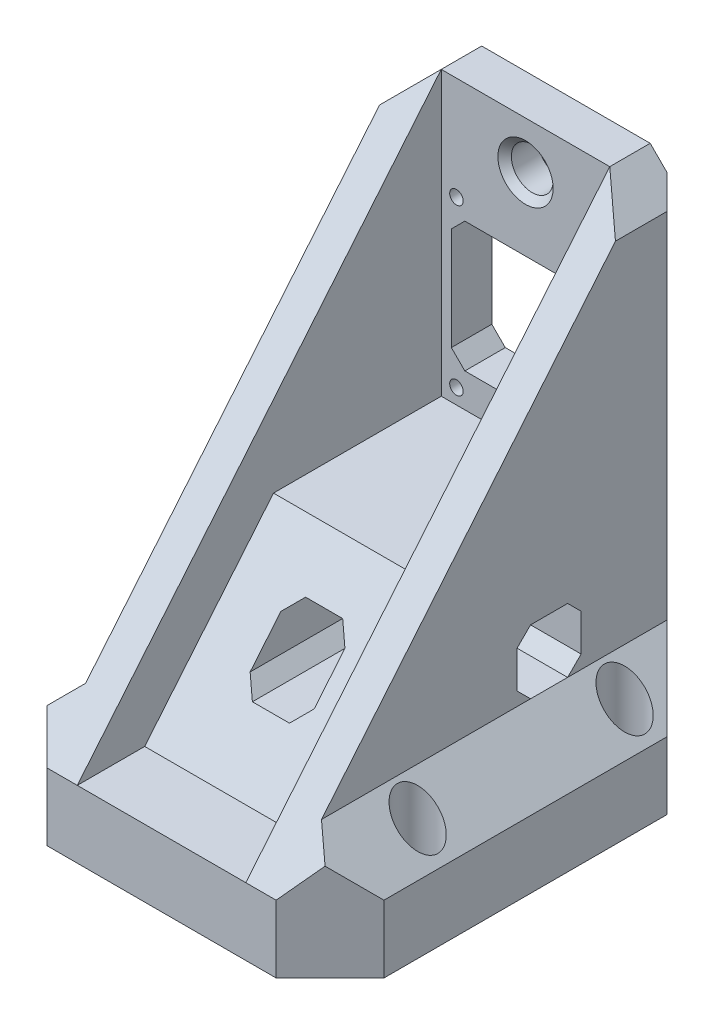
SolidWorks part; units mm, degrees
ref_plane "Front Plane" through (0, 0, 0) normal (0, 0, 1) x (1, 0, 0)
ref_plane "Top Plane" through (0, 0, 0) normal (0, 1, 0) x (1, 0, 0)
ref_plane "Right Plane" through (0, 0, 0) normal (1, 0, 0) x (0, 0, -1)
sketch "Sketch1" plane through (0, 0, 0) normal (0, 1, 0) x (1, 0, 0)
  line L1 (-25, 30) -> (25, 30)
  line L2 (-25, 30) -> (-25, -30)
  line L3 (-25, -30) -> (25, -30)
  line L4 (25, 30) -> (25, -30)
  line L5 (-25, 30) -> (25, -30) construction
  line L6 (-25, -30) -> (25, 30) construction
  point P0 (0, 0)
  dimension "D1" = 50
  dimension "D2" = 60
extrude "Boss-Extrude1" add sketch "Sketch1" along normal blind 10
sketch "Sketch2" plane through (0, 0, 0) normal (0, 1, 0) x (1, 0, 0)
  line L0 (-25, -30) -> (25, -30) construction
  line L1 (-21, -13) -> (21, -13) construction
  line L2 (-21, -13) -> (-21, 17.7) construction
  line L3 (-21, 17.7) -> (21, 17.7) construction
  line L4 (21, -13) -> (21, 17.7) construction
  line L5 (-21, -13) -> (21, 17.7) construction
  line L6 (-21, 17.7) -> (21, -13) construction
  circle A0 centre (-21, 17.7) radius 1.5
  circle A1 centre (-21, -13) radius 1.5
  circle A2 centre (21, 17.7) radius 1.5
  circle A3 centre (21, -13) radius 1.5
  point P0 (0, 2.35)
  dimension "D4" = 3
  dimension "D1" = 42
  dimension "D2" = 30.7
  dimension "D3" = 17
extrude "Cut-Extrude1" cut sketch "Sketch2" along normal blind 6
sketch "Sketch3" plane through (0, 6, 0) normal (0, -1, 0) x (1, 0, 0)
  circle A0 centre (-21, 13) radius 3
  circle A1 centre (21, 13) radius 3
  circle A2 centre (21, -17.7) radius 3
  circle A3 centre (-21, -17.7) radius 3
  dimension "D1" = 6
extrude "Cut-Extrude2" cut sketch "Sketch3" against normal up to next
sketch "Sketch5" plane through (0, 10, 0) normal (0, 1, 0) x (1, 0, 0)
  line L0 (25, 30) -> (-25, 30) construction
  line L1 (-12.5, 24) -> (12.5, 24)
  line L2 (-12.5, 24) -> (-12.5, 30)
  line L3 (-12.5, 30) -> (12.5, 30)
  line L4 (12.5, 24) -> (12.5, 30)
  line L5 (-12.5, 24) -> (12.5, 30) construction
  line L6 (-12.5, 30) -> (12.5, 24) construction
  point P0 (0, 27)
  dimension "D1" = 6
  dimension "D2" = 25
extrude "Boss-Extrude3" add sketch "Sketch5" along normal blind 65
sketch "Sketch6" plane through (0, 0, -30) normal (0, 0, -1) x (-1, 0, 0)
  line L1 (-11, 38) -> (11, 38)
  line L2 (-11, 38) -> (-11, 57.25)
  line L3 (-11, 57.25) -> (11, 57.25)
  line L4 (11, 38) -> (11, 57.25)
  line L5 (-11, 38) -> (11, 57.25) construction
  line L6 (-11, 57.25) -> (11, 38) construction
  line L7 (-12.5, 75) -> (12.5, 75) construction
  point P0 (0, 47.625)
  dimension "D1" = 22
  dimension "D2" = 19.25
  dimension "D3" = 17.75
extrude "Cut-Extrude3" cut sketch "Sketch6" against normal up to next
sketch "Sketch7" plane through (0, 0, -24) normal (0, 0, 1) x (1, 0, 0)
  line L1 (-10.25, 35.25) -> (10.25, 35.25) construction
  line L2 (-10.25, 35.25) -> (-10.25, 59.7) construction
  line L3 (-10.25, 59.7) -> (10.25, 59.7) construction
  line L4 (10.25, 35.25) -> (10.25, 59.7) construction
  line L5 (-10.25, 35.25) -> (10.25, 59.7) construction
  line L6 (-10.25, 59.7) -> (10.25, 35.25) construction
  line L7 (-12.5, 75) -> (12.5, 75) construction
  circle A0 centre (10.25, 35.25) radius 1
  circle A1 centre (-10.25, 35.25) radius 1
  circle A2 centre (-10.25, 59.7) radius 1
  circle A3 centre (10.25, 59.7) radius 1
  point P0 (0, 47.475)
  dimension "D4" = 2
  dimension "D1" = 20.5
  dimension "D2" = 24.45
  dimension "D3" = 15.3
extrude "Cut-Extrude4" cut sketch "Sketch7" against normal blind 2.5
sketch "Sketch8" plane through (0, 0, -26.5) normal (0, 0, 1) x (1, 0, 0)
  circle A0 centre (-10.25, 59.7) radius 2
  circle A1 centre (10.25, 59.7) radius 2
  circle A2 centre (10.25, 35.25) radius 2
  circle A3 centre (-10.25, 35.25) radius 2
  dimension "D1" = 4
extrude "Cut-Extrude5" cut sketch "Sketch8" against normal up to next
sketch "Sketch9" plane through (12.5, 0, 0) normal (1, 0, 0) x (0, 0, -1)
  line L0 (30, 75) -> (24, 75)
  line L4 (-30, 10) -> (30, 10)
  line L5 (30, 10) -> (30, 75)
  line L6 (30, 75) -> (30, 10) construction
  line L8 (-30, 10) -> (24, 75)
extrude "Boss-Extrude4" add sketch "Sketch9" along normal blind 5
mirror "Mirror1" about plane through (0, 0, 0) normal (1, 0, 0) of "Boss-Extrude4"
chamfer "Chamfer1" distance 7.5 angle 45 2 edges at (17.5, 10, 0) (-17.5, 10, 0)
chamfer "Chamfer2" distance 10 angle 45 2 edges at (-25, 5, -30) (25, 5, -30)
chamfer "Chamfer4" distance 5.5 angle 45 1 edges at (0, 0, -30)
chamfer "Chamfer5" distance 5 angle 45 2 edges at (17.5, 75, -25.75) (-17.5, 75, -25.75)
chamfer "Chamfer7" distance 2 angle 45 4 edges at (-11, 57.25, -27) (-11, 38, -27) (11, 38, -27) (11, 57.25, -27)
sketch "Sketch10" plane through (0, 0, -30) normal (0, 0, -1) x (-1, 0, 0)
  circle A0 centre (0, 68) radius 3.1
  circle A1 centre (-10.25, 59.7) radius 2 construction
  dimension "D1" = 6.2
  dimension "D2" = 8.3
extrude "Cut-Extrude6" cut sketch "Sketch10" against normal up to next
chamfer "Chamfer8" distance 1 angle 45 2 edges at (-3.1, 68, -24) (-3.1, 68, -30)
sketch "Sketch11" plane through (-12.5, 0, 0) normal (1, 0, 0) x (0, 0, -1)
  line L0 (-20, 10) -> (24, 10)
  line L1 (24, 10) -> (24, 33)
  line L2 (24, 75) -> (24, 10) construction
  line L3 (24, 33) -> (-0.8923, 33)
  line L4 (30, 38) -> (24, 38) construction
  line L5 (-0.8923, 33) -> (-20, 10)
  line L7 (19.8462, 70) -> (-23.7692, 17.5) construction
  line L9 (-30, 10) -> (20, 10) construction
  point P9 (-30, 10)
  dimension "D1" = 5
  dimension "D2" = 10
extrude "Boss-Extrude5" add sketch "Sketch11" along normal up to next
chamfer "Chamfer9" distance 8 angle 45 2 edges at (-25, 5, 30) (25, 5, 30)
sketch "Sketch12" plane through (0, 0, -30) normal (0, 0, -1) x (-1, 0, 0)
  line L1 (-4.75, 17.5) -> (4.75, 17.5)
  line L2 (-4.75, 17.5) -> (-4.75, 27)
  line L3 (-4.75, 27) -> (4.75, 27)
  line L4 (4.75, 17.5) -> (4.75, 27)
  line L5 (-4.75, 17.5) -> (4.75, 27) construction
  line L6 (-4.75, 27) -> (4.75, 17.5) construction
  line L7 (-12.5, 33) -> (12.5, 33) construction
  point P0 (0, 22.25)
  point P5 (5.4569, 11.207)
  point P6 (0, 0)
  point P7 (0, 20.319)
  point P8 (0, 24.3472)
  point P12 (0, 0)
  point P13 (-4.4578, 18.0844)
  point P14 (0, 0)
  dimension "D1" = 6
extrude "Cut-Extrude7" cut sketch "Sketch12" against normal up to next contours L2 L3 L4 L1
sketch "Sketch14" plane through (-4.75, 0, 0) normal (1, 0, 0) x (0, 0, -1)
  line L0 (-13.7692, 17.5) -> (30, 17.5) construction
  line L5 (30, 17.5) -> (30, 27) construction
  line L6 (-5.8769, 27) -> (30, 27) construction
  line L7 (5.25, 17.5) -> (14.75, 17.5)
  line L8 (5.25, 17.5) -> (5.25, 27)
  line L9 (5.25, 27) -> (14.75, 27)
  line L10 (14.75, 17.5) -> (14.75, 27)
  line L11 (5.25, 17.5) -> (14.75, 27) construction
  line L12 (5.25, 27) -> (14.75, 17.5) construction
  point P0 (10, 22.25)
  point P7 (14.4639, 18.1185)
  dimension "D1" = 20
extrude "Cut-Extrude9" cut sketch "Sketch14" against normal up to next
mirror "Mirror2" about plane through (0, 0, 0) normal (1, 0, 0) of "Cut-Extrude9"
chamfer "Chamfer11" distance 2 angle 45 20 edges at (11.125, 27, -14.75) (4.75, 27, -22.375) (4.75, 22.25, -14.75) (11.125, 17.5, -14.75) (4.75, 17.5, -22.375) (-11.125, 17.5, -14.75) (-4.75, 17.5, -22.375) (-4.75, 22.25, -14.75) (-11.125, 27, -14.75) (-4.75, 27, -22.375) (11.125, 17.5, -5.25) (4.75, 17.5, 4.2596) (4.75, 22.25, -5.25) (11.125, 27, -5.25) (4.75, 27, 0.3135) (-11.125, 17.5, -5.25) (-4.75, 17.5, 4.2596) (-4.75, 22.25, -5.25) (-11.125, 27, -5.25) (-4.75, 27, 0.3135)
